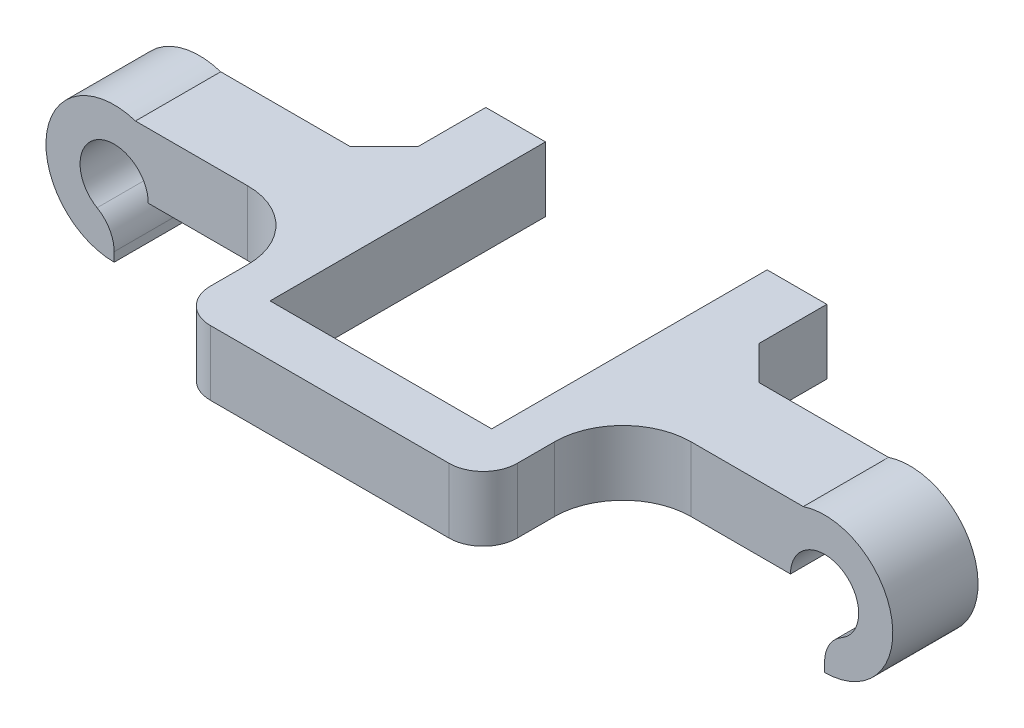
SolidWorks part; units mm, degrees
ref_plane "前视基准面" through (0, 0, 0) normal (0, 0, 1) x (1, 0, 0)
ref_plane "上视基准面" through (0, 0, 0) normal (0, 1, 0) x (1, 0, 0)
ref_plane "右视基准面" through (0, 0, 0) normal (1, 0, 0) x (0, 0, -1)
sketch "草图1" plane through (0, 0, 0) normal (0, 0, 1) x (1, 0, 0)
  line L0 (72.7521, 22.4325) -> (31.0821, 22.4325) construction
  line L1 (72.7521, 20.4325) -> (72.7521, 18.4325)
  line L2 (72.7521, 23.9325) -> (31.0821, 23.9325) construction
  line L3 (72.7521, 23.9325) -> (72.7521, 20.9325) construction
  line L4 (72.7521, 20.9325) -> (31.0821, 20.9325) construction
  line L5 (31.0821, 23.9325) -> (31.0821, 20.9325) construction
  line L6 (72.7521, 23.9325) -> (31.0821, 20.9325) construction
  line L7 (72.7521, 20.9325) -> (31.0821, 23.9325) construction
  line L8 (69.044, 23.9325) -> (34.7902, 23.9325)
  line L9 (70.7521, 22.4325) -> (33.0821, 22.4325)
  line L10 (31.0821, 20.4325) -> (31.0821, 18.4325)
  circle A0 centre (72.7521, 22.4325) radius 2 construction
  circle A1 centre (31.0821, 22.4325) radius 2 construction
  circle A2 centre (72.7521, 22.4325) radius 4 construction
  circle A3 centre (31.0821, 22.4325) radius 4 construction
  arc A4 (72.7521, 20.4325) -> (71.3208, 23.8294) centre (72.7521, 22.4325) ccw
  arc A5 (72.7521, 18.4325) -> (69.044, 23.9325) centre (72.7521, 22.4325) ccw
  arc A6 (71.3208, 23.8294) -> (70.7521, 22.4325) centre (72.7521, 22.4325) ccw
  arc A7 (34.7902, 23.9325) -> (31.0821, 18.4325) centre (31.0821, 22.4325) ccw
  arc A8 (33.0821, 22.4325) -> (31.0821, 20.4325) centre (31.0821, 22.4325) ccw
  point P6 (51.9171, 22.4325)
  dimension "D1" = 41.67
  dimension "D2" = 8
  dimension "D3" = 4
  dimension "D4" = 4
  dimension "D5" = 8
  dimension "D6" = 3
extrude "凸台-拉伸1" add sketch "草图1" along normal blind 28
sketch "草图2" plane through (0, 0, 28) normal (0, 0, 1) x (1, 0, 0)
  line L0 (34.033, 26.2325) -> (70.2894, 26.2325) construction
  line L1 (33.0821, 22.4325) -> (70.7521, 22.4325) construction
  line L2 (32.3311, 26.2325) -> (71.8047, 26.2325)
  line L3 (71.8047, 26.2325) -> (69.9484, 23.2922)
  line L4 (69.9484, 23.2922) -> (34.6282, 23.2922)
  line L5 (34.6282, 23.2922) -> (32.1673, 26.2325)
  line L6 (32.1673, 26.2325) -> (32.3311, 26.2325)
  arc A0 (34.7902, 23.9325) -> (31.0821, 18.4325) centre (31.0821, 22.4325) ccw construction
  dimension "D1" = 3.8
extrude "凸台-拉伸2" add sketch "草图2" against normal up to surface (28 mm away) up to face at (51.9171, 22.7826, 0)
sketch "草图3" plane through (0, 26.2325, 0) normal (0, 1, 0) x (1, 0, 0)
  line L0 (32.3311, -14) -> (69.4432, -14) construction
  line L1 (32.3311, 0) -> (71.5031, 0) construction
  line L2 (51.9171, -1.3937) -> (51.9171, -5.6688) construction
  line L4 (71.5031, -28) -> (32.3311, -28) construction
  line L5 (71.5031, 6) -> (32.3311, 6)
  line L6 (71.5031, 6) -> (71.5031, -34)
  line L7 (71.5031, -34) -> (32.3311, -34)
  line L8 (32.3311, 6) -> (32.3311, -34)
  line L9 (71.5031, 6) -> (32.3311, -34) construction
  line L10 (71.5031, -34) -> (32.3311, 6) construction
  point P2 (51.9171, -14)
  dimension "D1" = 6
  dimension "D2" = 6
extrude "凸台-拉伸3" add sketch "草图3" against normal blind 2
fillet "圆角1" radius 2 4 edges at (71.5031, 25.2325, -6) (32.3311, 25.2325, -6) (32.3311, 25.2325, 34) (71.5031, 25.2325, 34)
fillet "圆角2" radius 1 2 edges at (51.9171, 24.2325, 28) (51.9171, 24.2325, 0)
fillet "圆角3" radius 2 2 edges at (72.7521, 20.4325, 14) (31.0821, 20.4325, 14)
sketch "草图4" plane through (0, 26.2325, 0) normal (0, 1, 0) x (1, 0, 0)
  line L0 (51.9171, 6) -> (51.9171, -34) construction
  line L1 (69.5031, 6) -> (34.3311, 6) construction
  line L2 (34.3311, -34) -> (69.5031, -34) construction
  line L4 (39.4721, 3.415) -> (64.3621, 3.415) construction
  line L5 (39.4721, 3.415) -> (39.4721, -31.415) construction
  line L6 (39.4721, -31.415) -> (64.3621, -31.415) construction
  line L7 (64.3621, 3.415) -> (64.3621, -31.415) construction
  line L8 (39.4721, 3.415) -> (64.3621, -31.415) construction
  line L9 (39.4721, -31.415) -> (64.3621, 3.415) construction
  circle A0 centre (39.4721, 3.415) radius 1.1
  circle A1 centre (64.3621, 3.415) radius 1.1
  circle A2 centre (64.3621, -31.415) radius 1.1
  circle A3 centre (39.4721, -31.415) radius 1.1
  point P6 (51.9171, -14)
  dimension "D1" = 24.89
  dimension "D2" = 34.83
extrude "切除-拉伸1" cut sketch "草图4" against normal blind 2
sketch "草图5" plane through (0, 26.2325, 0) normal (0, 1, 0) x (1, 0, 0)
  line L0 (51.9171, 6.6377) -> (51.9171, -36.0645) construction
  line L1 (58.4171, -21.8526) -> (45.4171, -21.8526)
  line L2 (45.4171, -21.8526) -> (45.4171, -11.6621)
  line L3 (45.4171, -6.4716) -> (58.4171, -6.4716) construction
  line L4 (45.4171, -6.4716) -> (45.4171, -21.8526) construction
  line L5 (45.4171, -21.8526) -> (58.4171, -21.8526) construction
  line L6 (58.4171, -6.4716) -> (58.4171, -21.8526) construction
  line L7 (45.4171, -6.4716) -> (58.4171, -21.8526) construction
  line L8 (45.4171, -21.8526) -> (58.4171, -6.4716) construction
  line L9 (20.2631, -11.6621) -> (83.571, -11.6621) construction
  line L10 (20.2631, -11.6621) -> (20.2631, -16.6621) construction
  line L11 (20.2631, -16.6621) -> (83.571, -16.6621) construction
  line L12 (83.571, -11.6621) -> (83.571, -16.6621) construction
  line L13 (20.2631, -11.6621) -> (83.571, -16.6621) construction
  line L14 (20.2631, -16.6621) -> (83.571, -11.6621) construction
  line L15 (45.4171, -11.6621) -> (25.3764, -11.6621)
  line L16 (58.4171, -21.8526) -> (58.4171, -11.6621)
  line L17 (58.4171, -11.6621) -> (83.571, -11.6621)
  line L18 (83.571, -11.6621) -> (83.571, -16.6621)
  line L19 (83.571, -16.6621) -> (60.9171, -16.6621)
  line L20 (60.9171, -16.6621) -> (60.9171, -24.8526)
  line L21 (60.9171, -24.8526) -> (42.9171, -24.8526)
  line L23 (25.3764, -11.6621) -> (25.3764, -16.6621)
  line L24 (25.3764, -16.6621) -> (42.9171, -16.6621)
  line L25 (42.9171, -16.6621) -> (42.9171, -24.8526)
  point P1 (51.9171, -14.1621)
  point P7 (51.9171, -14.1621)
  dimension "D1" = 5
  dimension "D2" = 13
  dimension "D3" = 2.5
  dimension "D4" = 2.5
  dimension "D5" = 3
extrude "切除-拉伸2" cut sketch "草图5" against normal through all both and the other way through all flip side to cut
fillet "圆角4" radius 4 2 edges at (60.9171, 24.3325, 16.6621) (42.9171, 24.3325, 16.6621)
fillet "圆角5" radius 2 2 edges at (60.9171, 24.3325, 24.8526) (42.9171, 24.3325, 24.8526)
sketch "草图6" plane through (0, 26.2325, 0) normal (0, 1, 0) x (1, 0, 0)
  line L1 (45.4171, -11.6621) -> (41.9171, -11.6621)
  line L2 (45.4171, -11.6621) -> (45.4171, -5.6981)
  line L3 (45.4171, -5.6981) -> (41.9171, -5.6981)
  line L4 (41.9171, -11.6621) -> (41.9171, -5.6981)
  line L5 (58.4171, -11.6621) -> (61.9171, -11.6621)
  line L6 (58.4171, -11.6621) -> (58.4171, -5.6981)
  line L7 (58.4171, -5.6981) -> (61.9171, -5.6981)
  line L8 (61.9171, -11.6621) -> (61.9171, -5.6981)
  dimension "D1" = 3.5
  dimension "D2" = 3.5
extrude "凸台-拉伸4" add sketch "草图6" against normal up to surface (3.8 mm away) up to face at (51.9171, 22.4325, 18.3067)
chamfer "倒角1" distance 2 angle 45 2 edges at (61.9171, 24.3325, 11.6621) (41.9171, 24.3325, 11.6621)
